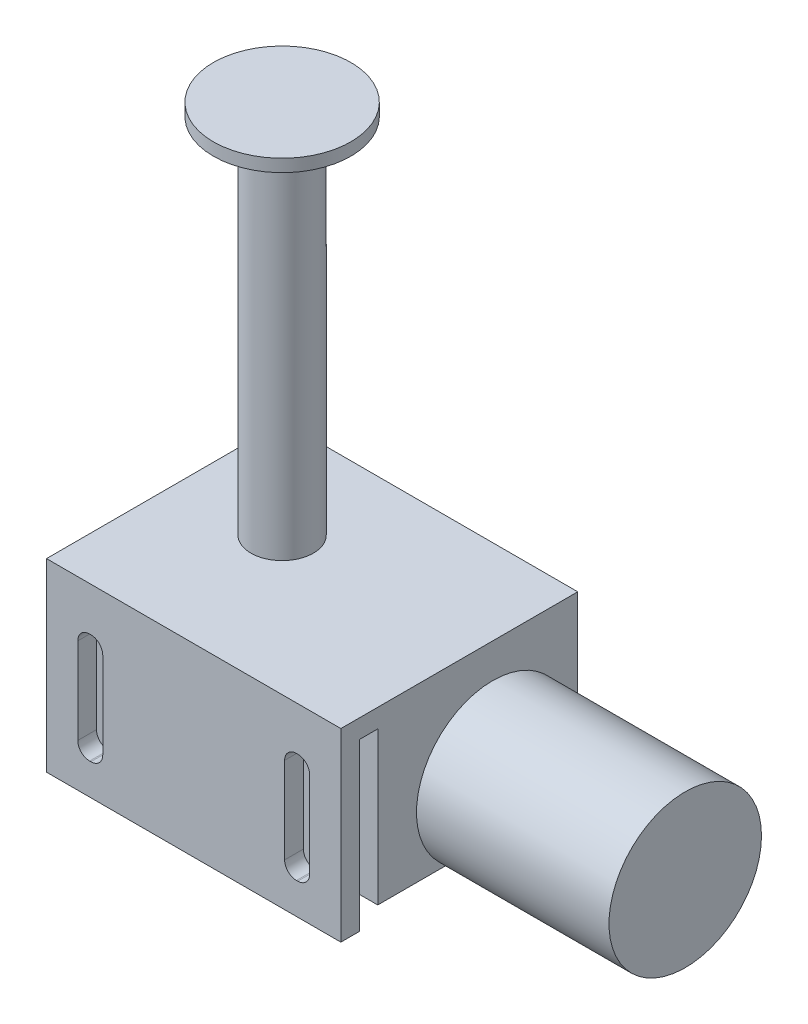
SolidWorks part; units mm, degrees
other "标注1"
sketch "草图20" plane through (-23.55, 25.1, 37.9) normal (-0.2277, 0.5156, 0.826) x (0.9602, 0.2599, 0.1025)
ref_plane "前视基准面" through (0, 0, 0) normal (0, 0, 1) x (1, 0, 0)
ref_plane "上视基准面" through (0, 0, 0) normal (0, 1, 0) x (1, 0, 0)
ref_plane "右视基准面" through (0, 0, 0) normal (1, 0, 0) x (0, 0, -1)
sketch "草图4" plane through (0, 0, 0) normal (0, 0, 1) x (1, 0, 0)
  line L1 (-23.55, 14.8) -> (23.55, 14.8)
  line L2 (-23.55, 14.8) -> (-23.55, -14.8)
  line L3 (-23.55, -14.8) -> (23.55, -14.8)
  line L4 (23.55, 14.8) -> (23.55, -14.8)
  line L5 (-23.55, 14.8) -> (23.55, -14.8) construction
  line L6 (-23.55, -14.8) -> (23.55, 14.8) construction
  point P0 (0, 0)
extrude "减速箱" add sketch "草图4" along normal blind 37.9
sketch "草图8" plane through (0, -14.8, 0) normal (0, -1, 0) x (1, 0, 0)
  line L1 (23.55, 37.9) -> (23.55, 0) construction
  line L2 (-23.55, 0) -> (23.55, 0)
  line L3 (-23.55, 0) -> (-23.55, 32)
  line L4 (-23.55, 32) -> (23.55, 32)
  line L5 (23.55, 0) -> (23.55, 32)
  dimension "D1" = 32
extrude "切除-拉伸1" cut sketch "草图8" against normal blind 2.2
sketch "草图12" plane through (0, -14.8, 0) normal (0, -1, 0) x (1, 0, 0)
  line L0 (23.55, 37.9) -> (23.55, 32) construction
  line L1 (-23.55, 32) -> (23.55, 32)
  line L2 (-23.55, 32) -> (-23.55, 34.9)
  line L3 (-23.55, 34.9) -> (23.55, 34.9)
  line L4 (23.55, 32) -> (23.55, 34.9)
  dimension "D1" = 2.9
extrude "固定凹槽" cut sketch "草图12" against normal offset from surface (26.6 mm away) 3 up to face at (0, 14.8, 18.95)
sketch "草图14" plane through (0, 0, 37.9) normal (0, 0, 1) x (1, 0, 0)
  line L0 (-23.55, 14.8) -> (-23.55, -14.8) construction
  line L3 (-23.55, -14.8) -> (23.55, -14.8) construction
  line L5 (23.55, 14.8) -> (-23.55, 14.8) construction
  line L9 (-14.55, 7.8) -> (-16.65, 7.8)
  line L10 (-14.55, 5.9) -> (-14.55, -7.9)
  line L11 (-16.45, -9.8) -> (-18.55, -9.8)
  line L12 (-18.55, 5.9) -> (-18.55, -7.9)
  arc A0 (-16.45, 7.8) -> (-14.55, 5.9) centre (-16.45, 5.9) cw
  arc A1 (-16.65, -9.8) -> (-18.55, -7.9) centre (-16.65, -7.9) cw
  arc A2 (-14.55, -7.9) -> (-16.45, -9.8) centre (-16.45, -7.9) cw
  arc A3 (-18.55, 5.9) -> (-16.65, 7.8) centre (-16.65, 5.9) cw
  point P0 (-23.55, 0)
  point P6 (-16.55, -14.8)
  point P11 (-16.55, 14.8)
  dimension "D6" = 1.9
  dimension "D1" = 7
  dimension "D2" = 5
  dimension "D3" = 5
  dimension "D4" = 4
extrude "切除-拉伸3" cut sketch "草图14" against normal up to surface (3 mm away) contours A3 L12 A1 L11 A2 L10 A0 L9 region at (-16.55, -1, 37.9) up to face at (0, -1.5, 34.9)
ref_plane "基准面8" through (-16.55, 0, 0) normal (1, 0, 0) x (0, 0, -1)
ref_plane "基准面7" through (0, 0, 0) normal (1, 0, 0) x (0, 0, -1)
mirror "镜向3" about plane through (0, 0, 0) normal (1, 0, 0) of "切除-拉伸3"
sketch "草图17" plane through (0, 14.8, 0) normal (0, 1, 0) x (1, 0, 0)
  line L0 (-23.55, 0) -> (-7.95, 0) construction
  line L1 (23.55, 0) -> (-23.55, 0) construction
  line L2 (-7.95, 0) -> (-7.95, -15.8) construction
  circle A0 centre (-7.95, -15.8) radius 5
  dimension "D3" = 10
  dimension "D1" = 15.6
  dimension "D2" = 15.8
extrude "传动轴" add sketch "草图17" along normal blind 60
sketch "草图19" plane through (23.55, 0, 0) normal (1, 0, 0) x (0, 0, -1)
  line L0 (0, -12.6) -> (0, -2.9) construction
  line L1 (0, -12.6) -> (0, 14.8) construction
  line L2 (0, -2.9) -> (-13.6, -2.9) construction
  circle A0 centre (-13.6, -2.9) radius 12.2
  dimension "D1" = 9.7
  dimension "D2" = 13.6
extrude "电机" add sketch "草图19" along normal blind 30.8
sketch "草图22" plane through (0, 74.8, 0) normal (0, 1, 0) x (1, 0, 0)
  circle A0 centre (-7.95, -15.8) radius 5 construction
  circle A1 centre (-7.95, -15.8) radius 11
  circle A2 centre (-7.95, -15.8) radius 5 construction
  point P6 (0, 0)
  point P7 (0, 0)
  dimension "D1" = 22
extrude "传动法兰" add sketch "草图22" against normal blind 2
